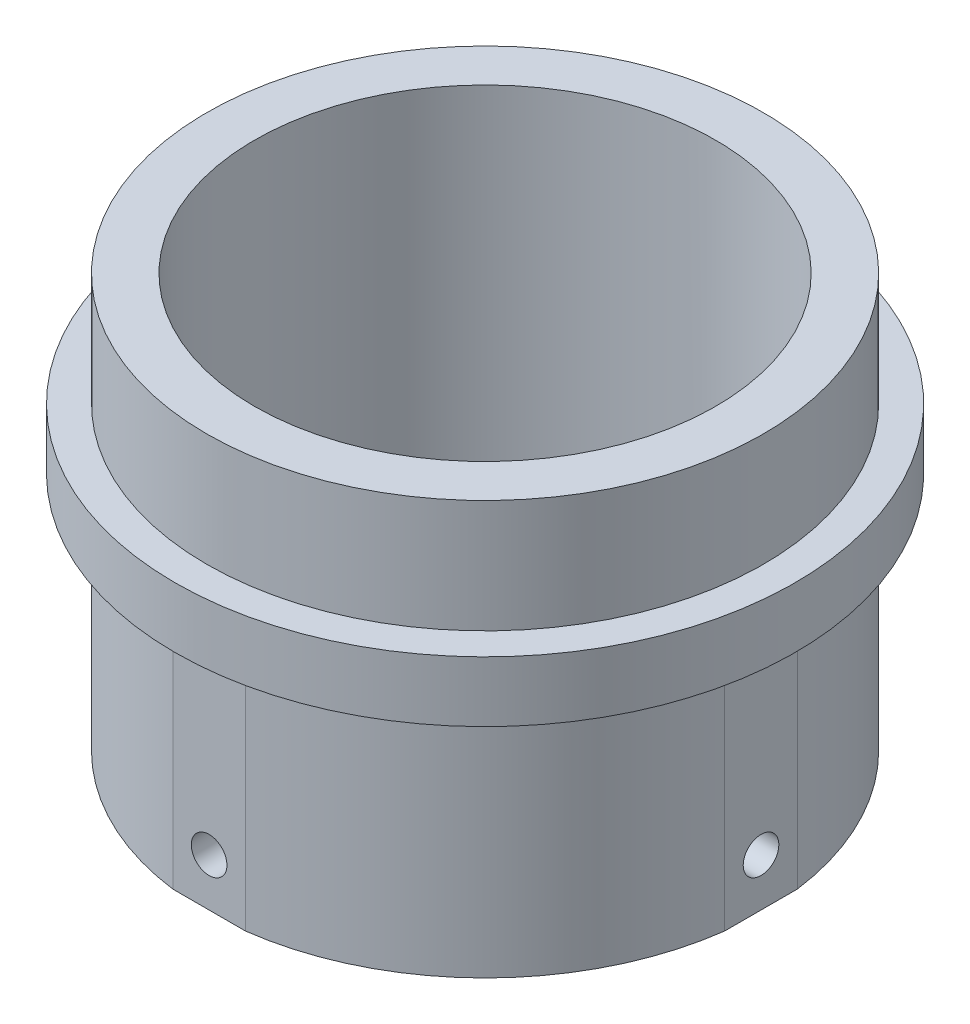
SolidWorks part; units mm, degrees
material "6061 Alloy"
ref_plane "Front Plane" through (0, 0, 0) normal (0, 0, 1) x (1, 0, 0)
ref_plane "Top Plane" through (0, 0, 0) normal (0, 1, 0) x (1, 0, 0)
ref_plane "Right Plane" through (0, 0, 0) normal (1, 0, 0) x (0, 0, -1)
sketch "Sketch1" plane through (0, 0, 0) normal (0, 1, 0) x (1, 0, 0)
  circle A0 centre (0, 0) radius 22.225
  circle A1 centre (0, 0) radius 18.415
  dimension "D1" = 44.45
  dimension "D2" = 3.81
extrude "Boss-Extrude1" add sketch "Sketch1" along normal blind 33.02
sketch "Sketch2" plane through (0, 0, 0) normal (0, 0, 1) x (1, 0, 0)
  line L0 (0, 0) -> (0, 3.81) construction
  circle A0 centre (0, 3.81) radius 1.4224
  dimension "D1" = 2.8448
  dimension "D2" = 3.81
extrude "Cut-Extrude1" cut sketch "Sketch2" against normal blind 43.18 and the other way blind 43.18
sketch "Sketch3" plane through (0, 0, 0) normal (1, 0, 0) x (0, 0, -1)
  line L0 (0, 0) -> (0, 3.81) construction
  circle A0 centre (0, 3.81) radius 1.4224
  dimension "D1" = 2.8448
extrude "Cut-Extrude2" cut sketch "Sketch3" against normal blind 43.18 and the other way blind 43.18
sketch "Sketch4" plane through (0, 0, 0) normal (0, -1, 0) x (1, 0, 0)
  line L1 (22.0345, -22.0345) -> (-22.0345, -22.0345)
  line L2 (22.0345, -22.0345) -> (22.0345, 22.0345)
  line L3 (22.0345, 22.0345) -> (-22.0345, 22.0345)
  line L4 (-22.0345, -22.0345) -> (-22.0345, 22.0345)
  line L5 (22.0345, -22.0345) -> (-22.0345, 22.0345) construction
  line L6 (22.0345, 22.0345) -> (-22.0345, -22.0345) construction
  line L7 (24.5128, -24.0002) -> (-24.5128, -24.0002)
  line L8 (24.5128, -24.0002) -> (24.5128, 24.0002)
  line L9 (24.5128, 24.0002) -> (-24.5128, 24.0002)
  line L10 (-24.5128, -24.0002) -> (-24.5128, 24.0002)
  line L11 (24.5128, -24.0002) -> (-24.5128, 24.0002) construction
  line L12 (24.5128, 24.0002) -> (-24.5128, -24.0002) construction
  point P0 (0, 0)
  point P6 (0, 0)
  dimension "D1" = 44.069
  dimension "D2" = 44.069
extrude "Cut-Extrude3" cut sketch "Sketch4" against normal blind 19.177
ref_plane "Plane1" through (0, 24.003, 0) normal (0, 1, 0) x (1, 0, 0)
sketch "Sketch5" plane through (0, 24.003, 0) normal (0, 1, 0) x (1, 0, 0)
  circle A0 centre (0, 0) radius 24.765
  circle A1 centre (0, 0) radius 18.415
  dimension "D1" = 49.53
extrude "Boss-Extrude2" add sketch "Sketch5" against normal blind 4.826
